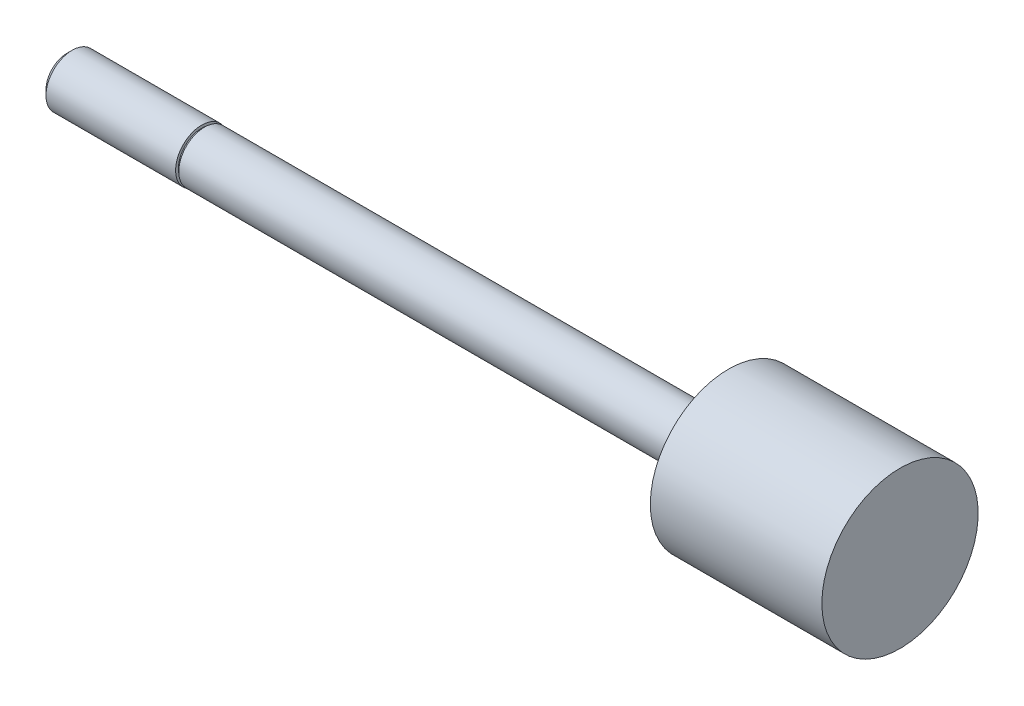
SolidWorks part; units mm, degrees
ref_plane "Front Plane" through (0, 0, 0) normal (0, 0, 1) x (1, 0, 0)
ref_plane "Top Plane" through (0, 0, 0) normal (0, 1, 0) x (1, 0, 0)
ref_plane "Right Plane" through (0, 0, 0) normal (1, 0, 0) x (0, 0, -1)
sketch "Sketch1" plane through (0, 0, 0) normal (0, 0, 1) x (1, 0, 0)
  line L0 (0, 0) -> (0, 2.3749)
  line L1 (0, 2.3749) -> (48.4124, 2.3749)
  line L2 (48.4124, 2.3749) -> (48.4124, 7.2199)
  line L3 (48.4124, 7.2199) -> (64.262, 7.2199)
  line L4 (64.262, 7.2199) -> (64.262, 0)
  line L5 (64.262, 0) -> (0, 0)
  line L6 (64.262, 0) -> (0, 0) construction
revolve "Revolve1" add sketch "Sketch1" angle 360 about L6 reverse direction yes
sketch "Sketch2" plane through (0, 0, 0) normal (0, 0, 1) x (1, 0, 0)
  line L0 (-12.7, 0) -> (-12.7, 1.9406)
  line L1 (-12.7, 1.9406) -> (-12.2276, 2.413)
  line L2 (-12.2276, 2.413) -> (0, 2.413)
  line L3 (0, 2.413) -> (0, 0)
  line L4 (0, 0) -> (-12.7, 0)
  line L5 (0, 0) -> (-12.7, 0) construction
revolve "Revolve2" add sketch "Sketch2" angle 360 about L5 reverse direction yes
cosmetic thread "Cosmetic Thread1" parameters "D1"=12.7, "D2"=3.8811
ref_plane "Plane1" through (0, 0, 0) normal (1, 0, 0) x (0, 0, -1)
ref_plane "Plane2" through (0, 0, 0) normal (1, 0, 0) x (0, 0, -1)
ref_plane "Plane3" through (112.6744, 0, 0) normal (1, 0, 0) x (0, 0, -1)
ref_plane "Plane4" through (-12.7, 0, 0) normal (1, 0, 0) x (0, 0, -1)
sketch "Sketch3" plane through (0, 0, 0) normal (0, 0, 1) x (1, 0, 0)
  line L0 (-0.254, 2.159) -> (0, 2.159)
  line L1 (0, 2.159) -> (0, 2.667)
  line L2 (0, 2.667) -> (-0.254, 2.667)
  line L3 (-0.254, 2.667) -> (-0.254, 2.159)
  line L4 (0, 0) -> (-0.254, 0) construction
revolve "Cut-Revolve1" cut sketch "Sketch3" angle 360 about L4 reverse direction yes
ref_plane "Plane5" through (0, 0, 0) normal (1, 0, 0) x (0, 0, -1)
ref_plane "Plane6" through (-12.7, 0, 0) normal (1, 0, 0) x (0, 0, -1)
ref_plane "dia1 XY" through (0, 0, 0) normal (1, 0, 0) x (0, 0, -1)
ref_plane "dia1 XZ" through (0, 2.3749, 0) normal (0, -1, 0) x (-1, 0, 0)
ref_plane "dia1 YZ" through (0, 0, 0) normal (0, 0, -1) x (-1, 0, 0)
ref_axis "dia1 X" through (0, 2.3749, 80.9) along (0, 0, -1)
ref_axis "dia1 Y" through (0, -50, 0) along (0, 1, 0)
ref_axis "dia1 Z" through (80.9, 2.3749, 0) along (-1, 0, 0)
sketch3d "dia1"
  point P0 (0, 2.3749, 0)
ref_plane "dia12 XY" through (0, 0, 0) normal (1, 0, 0) x (0, 0, -1)
ref_plane "dia12 XZ" through (0, 0, 0) normal (0, -1, 0) x (-1, 0, 0)
ref_plane "dia12 YZ" through (0, 0, 7.8105) normal (0, 0, -1) x (-1, 0, 0)
ref_axis "dia12 X" through (0, 0, 80.9) along (0, 0, -1)
ref_axis "dia12 Y" through (0, -50, 7.8105) along (0, 1, 0)
ref_axis "dia12 Z" through (80.9, 0, 7.8105) along (-1, 0, 0)
sketch3d "dia12"
  point P0 (0, 0, 7.8105)
ref_plane "dia2 XY" through (0, 0, 0) normal (1, 0, 0) x (0, 0, -1)
ref_plane "dia2 XZ" through (0, -2.3749, 0) normal (0, -1, 0) x (-1, 0, 0)
ref_plane "dia2 YZ" through (0, 0, 0) normal (0, 0, -1) x (-1, 0, 0)
ref_axis "dia2 X" through (0, -2.3749, 80.9) along (0, 0, -1)
ref_axis "dia2 Y" through (0, -50, 0) along (0, 1, 0)
ref_axis "dia2 Z" through (80.9, -2.3749, 0) along (-1, 0, 0)
sketch3d "dia2"
  point P0 (0, -2.3749, 0)
ref_plane "dia22 XY" through (0, 0, 0) normal (1, 0, 0) x (0, 0, -1)
ref_plane "dia22 XZ" through (0, 0, 0) normal (0, -1, 0) x (-1, 0, 0)
ref_plane "dia22 YZ" through (0, 0, -7.8105) normal (0, 0, -1) x (-1, 0, 0)
ref_axis "dia22 X" through (0, 0, 80.9) along (0, 0, -1)
ref_axis "dia22 Y" through (0, -50, -7.8105) along (0, 1, 0)
ref_axis "dia22 Z" through (80.9, 0, -7.8105) along (-1, 0, 0)
sketch3d "dia22"
  point P0 (0, 0, -7.8105)
ref_plane "rl1 XY" through (-12.7, 0, 0) normal (1, 0, 0) x (0, 0, -1)
ref_plane "rl1 XZ" through (0, 0, 0) normal (0, -1, 0) x (-1, 0, 0)
ref_plane "rl1 YZ" through (0, 0, 0) normal (0, 0, -1) x (-1, 0, 0)
ref_axis "rl1 X" through (-12.7, 0, 80.9) along (0, 0, -1)
ref_axis "rl1 Y" through (-12.7, -50, 0) along (0, 1, 0)
ref_axis "rl1 Z" through (80.9, 0, 0) along (-1, 0, 0)
sketch3d "rl1"
  point P0 (-12.7, 0, 0)
ref_plane "rl2 XY" through (0, 0, 0) normal (1, 0, 0) x (0, 0, -1)
ref_plane "rl2 XZ" through (0, 0, 0) normal (0, -1, 0) x (-1, 0, 0)
ref_plane "rl2 YZ" through (0, 0, 0) normal (0, 0, -1) x (-1, 0, 0)
ref_axis "rl2 X" through (0, 0, 80.9) along (0, 0, -1)
ref_axis "rl2 Y" through (0, -50, 0) along (0, 1, 0)
ref_axis "rl2 Z" through (80.9, 0, 0) along (-1, 0, 0)
sketch3d "rl2"
  point P0 (0, 0, 0)
ref_plane "rod_cp XY" through (0, 0, 0) normal (1, 0, 0) x (0, 0, -1)
ref_plane "rod_cp XZ" through (0, 0, 0) normal (0, -1, 0) x (-1, 0, 0)
ref_plane "rod_cp YZ" through (0, 0, 0) normal (0, 0, -1) x (-1, 0, 0)
ref_axis "rod_cp X" through (0, 0, 80.9) along (0, 0, -1)
ref_axis "rod_cp Y" through (0, -50, 0) along (0, 1, 0)
ref_axis "rod_cp Z" through (80.9, 0, 0) along (-1, 0, 0)
sketch3d "rod_cp"
  point P0 (0, 0, 0)
ref_plane "thd1 XY" through (-12.7, 0, 0) normal (1, 0, 0) x (0, 0, -1)
ref_plane "thd1 XZ" through (0, 2.413, 0) normal (0, -1, 0) x (-1, 0, 0)
ref_plane "thd1 YZ" through (0, 0, 0) normal (0, 0, -1) x (-1, 0, 0)
ref_axis "thd1 X" through (-12.7, 2.413, 80.9) along (0, 0, -1)
ref_axis "thd1 Y" through (-12.7, -50, 0) along (0, 1, 0)
ref_axis "thd1 Z" through (80.9, 2.413, 0) along (-1, 0, 0)
sketch3d "thd1"
  point P0 (-12.7, 2.413, 0)
ref_plane "thd2 XY" through (-12.7, 0, 0) normal (1, 0, 0) x (0, 0, -1)
ref_plane "thd2 XZ" through (0, -2.413, 0) normal (0, -1, 0) x (-1, 0, 0)
ref_plane "thd2 YZ" through (0, 0, 0) normal (0, 0, -1) x (-1, 0, 0)
ref_axis "thd2 X" through (-12.7, -2.413, 80.9) along (0, 0, -1)
ref_axis "thd2 Y" through (-12.7, -50, 0) along (0, 1, 0)
ref_axis "thd2 Z" through (80.9, -2.413, 0) along (-1, 0, 0)
sketch3d "thd2"
  point P0 (-12.7, -2.413, 0)
ref_plane "to_rod_clevis XY" through (-12.7, 0, 0) normal (1, 0, 0) x (0, 0, -1)
ref_plane "to_rod_clevis XZ" through (0, 0, 0) normal (0, -1, 0) x (-1, 0, 0)
ref_plane "to_rod_clevis YZ" through (0, 0, 0) normal (0, 0, -1) x (-1, 0, 0)
ref_axis "to_rod_clevis X" through (-12.7, 0, 80.9) along (0, 0, -1)
ref_axis "to_rod_clevis Y" through (-12.7, -50, 0) along (0, 1, 0)
ref_axis "to_rod_clevis Z" through (80.9, 0, 0) along (-1, 0, 0)
sketch3d "to_rod_clevis"
  point P0 (-12.7, 0, 0)
